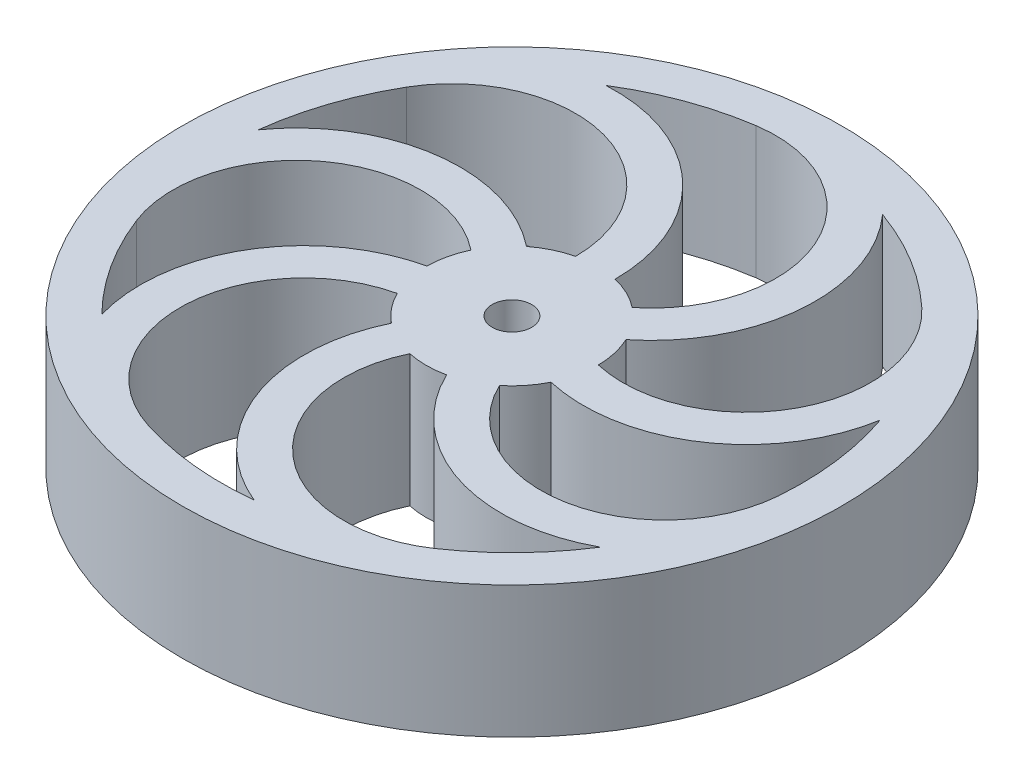
SolidWorks part; units mm, degrees
material "Rubber"
ref_plane "Front Plane" through (0, 0, 0) normal (0, 0, 1) x (1, 0, 0)
ref_plane "Top Plane" through (0, 0, 0) normal (0, 1, 0) x (1, 0, 0)
ref_plane "Right Plane" through (0, 0, 0) normal (1, 0, 0) x (0, 0, -1)
sketch "Base Reference Sketch" plane through (0, 0, 0) normal (0, 1, 0) x (1, 0, 0)
  line L0 (-1.5, 6.3246) -> (1.5, 6.3246) construction
  circle A0 centre (0, 0) radius 25
  circle A1 centre (0, 0) radius 22
  circle A2 centre (0, 0) radius 1.5
  circle A3 centre (0, 0) radius 6.5
  arc A4 (-1.5, 6.3246) -> (-19.0283, 11.0419) centre (-10.8989, 6.3246) ccw
  arc A5 (1.5, 6.3246) -> (-11.5817, 18.7047) centre (-10.8989, 6.3246) ccw
  arc A6 (1.5, 6.3246) -> (-21.623, 12.5477) centre (-10.8989, 6.3246) ccw construction
  point P11 (0, 6.3246)
  dimension "D1" = 50
  dimension "D3" = 5
  dimension "D2" = 3
  dimension "D4" = 3
  dimension "D5" = 3
extrude "Base Wheel Extrude" add sketch "Base Reference Sketch" along normal blind 10 contours A0 A1 | A3 A5 A1 A4 | A3 A2 region at (-24.2929, 0, 0) region at (-2.5412, 0, -15.1559) region at (4.9548, 0, -3.9171)
pattern_circular "Spokes Circular Pattern" count 7 over 360 about axis through (0, 10, 0) along (0, -1, 0) of "Base Wheel Extrude"
equation "\"wheeldia\"= 50mm"
equation "\"wheelthick\"= 3mm"
equation "\"wheelwide\"= 10mm"
equation "\"wheelspokes\"= 7"
